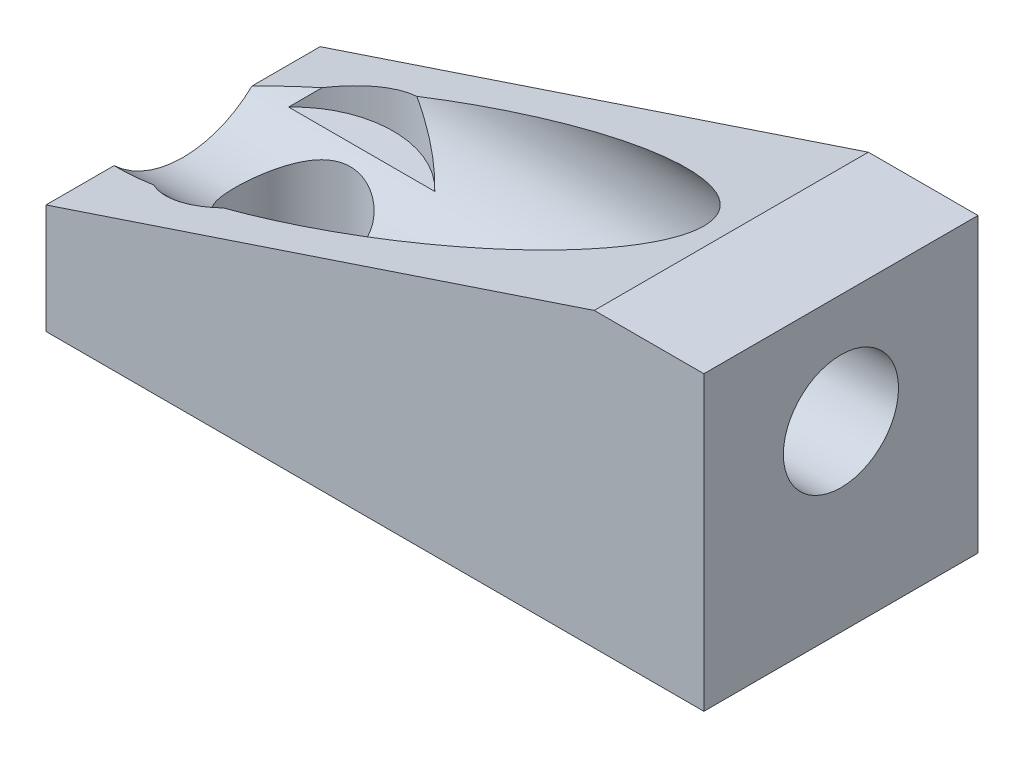
SolidWorks part; units mm, degrees
ref_plane "Front Plane" through (0, 0, 0) normal (0, 0, 1) x (1, 0, 0)
ref_plane "Top Plane" through (0, 0, 0) normal (0, 1, 0) x (1, 0, 0)
ref_plane "Right Plane" through (0, 0, 0) normal (1, 0, 0) x (0, 0, -1)
sketch "Sketch3" plane through (0, 0, 0) normal (0, 0, 1) x (1, 0, 0)
  line L0 (2.3468, 0) -> (38.3468, 0)
  line L1 (55, 0) -> (-55, 0) construction
  line L2 (38.3468, 0) -> (38.3468, 16)
  line L4 (2.3468, 0) -> (2.3468, 6)
  line L6 (38.3468, 16) -> (32.3468, 16)
  line L8 (2.3468, 6) -> (32.3468, 16)
  dimension "D1" = 36
  dimension "D2" = 16
  dimension "D3" = 6
  dimension "D4" = 6
extrude "Boss-Extrude2" add sketch "Sketch3" along normal blind 15 contours L4 | L2 L0 region at (23.1637, 6.3568, 0)
ref_plane "Plane1" through (0, 20, 0) normal (0, 1, 0) x (1, 0, 0)
sketch "Sketch4" plane through (0, 20, 0) normal (0, 1, 0) x (1, 0, 0)
  line L1 (38.3468, -15) -> (38.3468, 0) construction
  line L2 (-8.8, 0) -> (8.8, 0) construction
  circle A0 centre (8.3468, -7.5) radius 3.15
  circle A1 centre (8.3468, -7.5) radius 5.5
  dimension "D1" = 6.3
  dimension "D2" = 11
  dimension "D3" = 30
  dimension "D4" = 7.5
extrude "Cut-Extrude1" cut sketch "Sketch4" against normal through all contours A0 region at (8.3468, 20, 7.5)
extrude "Cut-Extrude2" cut sketch "Sketch4<3>" against normal blind 14
sketch "Sketch4<3>" plane through (0, 20, 0) normal (0, 1, 0) x (1, 0, 0) same geometry as "Sketch4"
sketch "Sketch6" plane through (0, 0, 0) normal (1, 0, 0) x (0, 0, -1)
  line L1 (8.25, 0) -> (-8.25, 0) construction
  line L2 (-15, 0) -> (-15, 16) construction
  circle A0 centre (-7.5, 10) radius 3.15
  circle A1 centre (-7.5, 10) radius 5.5
  dimension "D1" = 6.3
  dimension "D2" = 11
  dimension "D3" = 10
  dimension "D4" = 7.5
extrude "Cut-Extrude3" cut sketch "Sketch6" along normal through all contours A0 region at (0, 10, 7.5)
extrude "Cut-Extrude4" cut sketch "Sketch6<3>" along normal offset from surface (32.3468 mm away) 6 up to face at (38.3468, 10, 4.35)
sketch "Sketch6<3>" plane through (0, 0, 0) normal (1, 0, 0) x (0, 0, -1) same geometry as "Sketch6"
